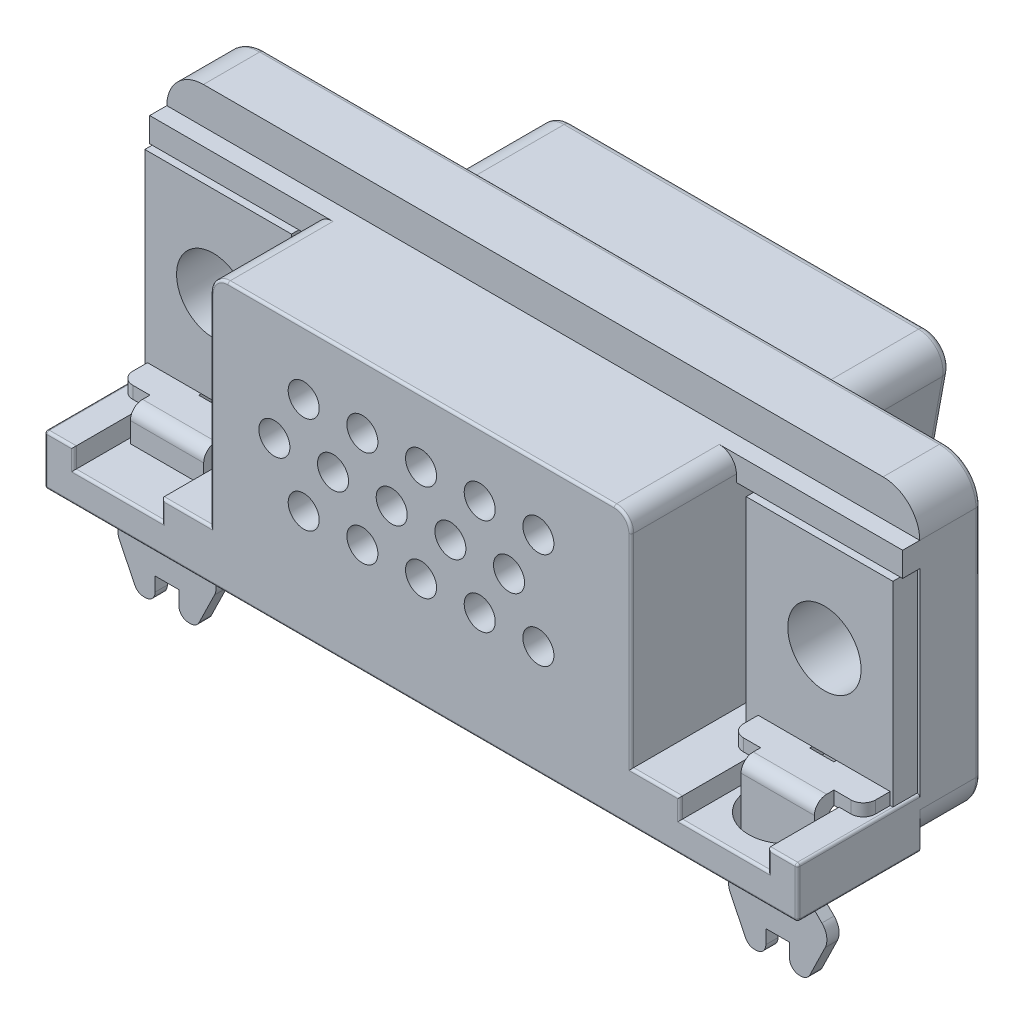
SolidWorks part; units mm, degrees
ref_plane "Спереди" through (0, 0, 0) normal (0, 0, 1) x (1, 0, 0)
ref_plane "Сверху" through (0, 0, 0) normal (0, 1, 0) x (1, 0, 0)
ref_plane "Справа" through (0, 0, 0) normal (1, 0, 0) x (0, 0, -1)
sketch "Эскиз1" plane through (0, 0, 0) normal (0, 0, 1) x (1, 0, 0)
  line L1 (-13.9, -6.275) -> (13.9, -6.275)
  line L2 (-15.4, -4.775) -> (-15.4, 4.775)
  line L3 (-13.9, 6.275) -> (13.9, 6.275)
  line L4 (15.4, -4.775) -> (15.4, 4.775)
  line L5 (-15.4, -6.275) -> (15.4, 6.275) construction
  line L6 (-15.4, 6.275) -> (15.4, -6.275) construction
  arc A0 (13.9, -6.275) -> (15.4, -4.775) centre (13.9, -4.775) ccw
  arc A1 (13.9, 6.275) -> (15.4, 4.775) centre (13.9, 4.775) cw
  arc A2 (-13.9, -6.275) -> (-15.4, -4.775) centre (-13.9, -4.775) cw
  arc A3 (-15.4, 4.775) -> (-13.9, 6.275) centre (-13.9, 4.775) cw
  point P0 (0, 0)
  dimension "D3" = 1.5
  dimension "D1" = 30.8
  dimension "D2" = 12.55
extrude "Бобышка-Вытянуть1" add sketch "Эскиз1" along normal blind 2.5
sketch "Эскиз2" plane through (0, 0, 2.5) normal (0, 0, 1) x (1, 0, 0)
  line L0 (-8.6, -4.225) -> (-8.6, 4.775)
  line L1 (0, 6.275) -> (0, -6.275) construction
  line L2 (13.9, 6.275) -> (-13.9, 6.275) construction
  line L3 (-13.9, -6.275) -> (13.9, -6.275) construction
  line L4 (-8.6, 4.775) -> (8.6, 4.775)
  line L5 (-15.4, 4.775) -> (-15.4, -4.775) construction
  line L6 (8.6, 4.775) -> (8.6, -4.225)
  line L7 (-8.6, -4.225) -> (-10.6, -4.225)
  line L8 (-15.4, -4.225) -> (-15.4, -6.275)
  line L9 (-15.4, -6.275) -> (15.4, -6.275)
  line L10 (8.6, -4.225) -> (10.6, -4.225)
  line L11 (-10.6, -5.0477) -> (-14.2, -5.0477)
  line L12 (15.4, -4.775) -> (15.4, 4.775) construction
  line L13 (-14.2, -5.0477) -> (-14.2, -4.225)
  line L14 (-14.2, -4.225) -> (-15.4, -4.225)
  line L15 (10.6, -5.0477) -> (10.6, -4.225)
  line L16 (10.6, -5.0477) -> (14.2, -5.0477)
  line L17 (14.2, -5.0477) -> (14.2, -4.225)
  line L18 (14.2, -4.225) -> (15.4, -4.225)
  line L19 (15.4, -4.225) -> (15.4, -6.275)
  line L21 (-10.6, -5.0477) -> (-10.6, -4.225)
  dimension "D1" = 9
  dimension "D2" = 17.2
  dimension "D3" = 1.5
  dimension "D4" = 1.2
  dimension "D5" = 0.8227
  dimension "D6" = 3.6
  dimension "D7" = 1.2273
extrude "Бобышка-Вытянуть3" add sketch "Эскиз2" along normal blind 5
sketch "Эскиз3" plane through (0, 0, 2.5) normal (0, 0, 1) x (1, 0, 0)
  line L0 (-6.6576, 4.775) -> (-15.4, 4.775) construction
  line L1 (8.6, 4.775) -> (-8.6, 4.775) construction
  line L2 (-15.4, 4.775) -> (15.4, 4.775)
  line L3 (-15.4, 4.775) -> (-15.4, 3.775)
  line L4 (-15.4, 4.775) -> (-15.4, -4.225) construction
  line L5 (-15.4, 3.775) -> (15.4, 3.775)
  line L6 (15.4, -4.225) -> (15.4, 4.775) construction
  line L7 (15.4, 3.775) -> (15.4, 4.775)
  dimension "D1" = 1
extrude "Бобышка-Вытянуть4" add sketch "Эскиз3" along normal blind 0.7
fillet "Скругление1" radius 0.7 2 edges at (8.6, 4.775, 5.35) (-8.6, 4.775, 5.35)
sketch "Эскиз4" plane through (0, 0, 0) normal (0, 0, -1) x (-1, 0, 0)
  line L0 (0, 6.275) -> (0, -6.275) construction
  line L1 (-13.9, 6.275) -> (13.9, 6.275) construction
  line L2 (13.9, -6.275) -> (-13.9, -6.275) construction
  line L3 (-7.2498, 4.1305) -> (7.2498, 4.1305)
  line L4 (-6.1668, -3.7695) -> (6.1668, -3.7695)
  line L5 (-8.2333, 2.95) -> (-7.1504, -2.95)
  line L6 (8.2333, 2.95) -> (7.1504, -2.95)
  line L7 (-7.6919, 0) -> (7.6919, 0) construction
  arc A0 (6.1668, -3.7695) -> (7.1504, -2.95) centre (6.1668, -2.7695) ccw
  arc A1 (-6.1668, -3.7695) -> (-7.1504, -2.95) centre (-6.1668, -2.7695) cw
  arc A2 (7.2498, 4.1305) -> (8.2333, 2.95) centre (7.2498, 3.1305) cw
  arc A3 (-7.2498, 4.1305) -> (-8.2333, 2.95) centre (-7.2498, 3.1305) ccw
  point P8 (0, 4.1305)
  point P11 (0, -3.7695)
  point P17 (7, -3.7695)
  point P20 (-7, -3.7695)
  point P23 (8.45, 4.1305)
  point P26 (-8.45, 4.1305)
  dimension "D4" = 1
  dimension "D1" = 16.9
  dimension "D2" = 14
  dimension "D3" = 7.9
extrude "Бобышка-Вытянуть5" add sketch "Эскиз4" along normal blind 5.9
sketch "Эскиз5" plane through (0, 0, -5.9) normal (0, 0, -1) x (-1, 0, 0)
  line L8 (6.6586, -2.8597) -> (7.7415, 3.0403)
  line L9 (7.2498, 3.6305) -> (-7.2498, 3.6305)
  line L10 (-7.7415, 3.0403) -> (-6.6586, -2.8597)
  line L11 (-6.1668, -3.2695) -> (6.1668, -3.2695)
  line L12 (6.6586, -2.8597) -> (7.7415, 3.0403)
  line L13 (7.2498, 3.6305) -> (-7.2498, 3.6305)
  line L14 (-7.7415, 3.0403) -> (-6.6586, -2.8597)
  line L15 (-6.1668, -3.2695) -> (6.1668, -3.2695)
  arc A8 (6.1668, -3.2695) -> (6.6586, -2.8597) centre (6.1668, -2.7695) ccw
  arc A9 (7.7415, 3.0403) -> (7.2498, 3.6305) centre (7.2498, 3.1305) ccw
  arc A10 (-7.2498, 3.6305) -> (-7.7415, 3.0403) centre (-7.2498, 3.1305) ccw
  arc A11 (-6.6586, -2.8597) -> (-6.1668, -3.2695) centre (-6.1668, -2.7695) ccw
  arc A12 (6.1668, -3.2695) -> (6.6586, -2.8597) centre (6.1668, -2.7695) ccw
  arc A13 (7.7415, 3.0403) -> (7.2498, 3.6305) centre (7.2498, 3.1305) ccw
  arc A14 (-7.2498, 3.6305) -> (-7.7415, 3.0403) centre (-7.2498, 3.1305) ccw
  arc A15 (-6.6586, -2.8597) -> (-6.1668, -3.2695) centre (-6.1668, -2.7695) ccw
  dimension "D1" = 0.5
extrude "Вырез-Вытянуть1" cut sketch "Эскиз5" against normal blind 0.1
fillet "Скругление2" radius 0.3 16 edges at (-8.018, 3.7706, -5.9) (-7.6919, 0, -5.9) (-6.8069, -3.5378, -5.9) (0, -3.7695, -5.9) (6.8069, -3.5378, -5.9) (7.6919, 0, -5.9) (8.018, 3.7706, -5.9) (0, 4.1305, -5.9) (-8.018, 3.7706, 0) (-7.6919, 0, 0) (-6.8069, -3.5378, 0) (0, -3.7695, 0) (6.8069, -3.5378, 0) (7.6919, 0, 0) (8.018, 3.7706, 0) (0, 4.1305, 0)
sketch "Эскиз6" plane through (0, 0, 0) normal (0, 0, -1) x (-1, 0, 0)
  line L0 (-15.4, 0) -> (15.4, 0) construction
  line L1 (-15.4, -4.775) -> (-15.4, 4.775) construction
  line L2 (15.4, 4.775) -> (15.4, -4.775) construction
  circle A0 centre (-12.5, 0) radius 1.5
  circle A1 centre (12.5, 0) radius 1.5
  dimension "D3" = 3
  dimension "D1" = 12.5
  dimension "D2" = 12.5
extrude "Вырез-Вытянуть2" cut sketch "Эскиз6" against normal through all
sketch "Эскиз7" plane through (0, 0, -5.8) normal (0, 0, -1) x (-1, 0, 0)
  line L0 (7.2498, 3.6305) -> (-7.2498, 3.6305) construction
  line L2 (0, 3.6305) -> (0, -3.2695) construction
  line L3 (-6.1668, -3.2695) -> (6.1668, -3.2695) construction
  line L5 (-4.8, 2.1705) -> (-2.4, 2.1705) construction
  line L6 (-3.6, 2.1705) -> (-3.6, -3.2695) construction
  line L7 (-15.4, -4.775) -> (-15.4, 4.775) construction
  circle A0 centre (-4.8, 2.1705) radius 0.635
  circle A1 centre (-2.4, 2.1705) radius 0.635
  circle A2 centre (0, 2.1705) radius 0.635
  circle A3 centre (2.4, 2.1705) radius 0.635
  circle A4 centre (4.8, 2.1705) radius 0.635
  circle A5 centre (-3.6, 0.1905) radius 0.635
  circle A6 centre (-4.8, -1.7895) radius 0.635
  circle A7 centre (-1.2, 0.1905) radius 0.635
  circle A8 centre (1.2, 0.1905) radius 0.635
  circle A9 centre (3.6, 0.1905) radius 0.635
  circle A10 centre (6, 0.1905) radius 0.635
  circle A11 centre (-2.4, -1.7895) radius 0.635
  circle A12 centre (0, -1.7895) radius 0.635
  circle A13 centre (2.4, -1.7895) radius 0.635
  circle A14 centre (4.8, -1.7895) radius 0.635
  dimension "D1" = 1.27
  dimension "D7" = 1.27
  dimension "D2" = 1.46
  dimension "D3" = 10.6
  dimension "D5" = 2.4
  dimension "D6" = 1.98
  dimension "D8" = 1.98
  dimension "D9" = 5
  dimension "D10" = 1.46
  dimension "D11" = 2.4
  dimension "D12" = 1.98
  dimension "D14" = 2.4
  dimension "D15" = 1.98
  dimension "D16" = 10.6
  dimension "D4" = 5
  dimension "D13" = 5
extrude "Вырез-Вытянуть3" cut sketch "Эскиз7" against normal blind 16.1
fillet "Скругление3" radius 0.15 15 edges at (-5.435, -1.7895, -5.8) (-3.035, -1.7895, -5.8) (-0.635, -1.7895, -5.8) (1.765, -1.7895, -5.8) (4.165, -1.7895, -5.8) (2.965, 0.1905, -5.8) (0.565, 0.1905, -5.8) (-1.835, 0.1905, -5.8) (-4.235, 0.1905, -5.8) (-6.635, 0.1905, -5.8) (-5.435, 2.1705, -5.8) (-3.035, 2.1705, -5.8) (-0.635, 2.1705, -5.8) (1.765, 2.1705, -5.8) (4.165, 2.1705, -5.8)
fillet "Скругление4" radius 0.3 2 edges at (11, 0, 0) (-14, 0, 0)
sketch "Эскиз8" plane through (0, -6.275, 0) normal (0, -1, 0) x (1, 0, 0)
  line L0 (0, 7.5) -> (0, 0) construction
  line L1 (-15.4, 7.5) -> (15.4, 7.5) construction
  line L2 (-13.9, 0) -> (13.9, 0) construction
  circle A0 centre (-12.5, 11.4) radius 1.6
  circle A1 centre (12.5, 5) radius 1.6
  dimension "D1" = 3.2
  dimension "D2" = 12.5
  dimension "D3" = 12.5
  dimension "D4" = 11.4
  dimension "D5" = 5
extrude "Вырез-Вытянуть4" cut sketch "Эскиз8" against normal blind 9.1
fillet "Скругление5" radius 0.2 8 edges at (14.9607, 5.8357, 0) (15.4, 0, 0) (14.9607, -5.8357, 0) (0, -6.275, 0) (-14.9607, -5.8357, 0) (-15.4, 0, 0) (-14.9607, 5.8357, 0) (0, 6.275, 0)
sketch "Эскиз9" plane through (0, 0, 2.5) normal (0, 0, 1) x (1, 0, 0)
  line L0 (-15.3, 3.775) -> (-15.3, -4.225)
  line L1 (-15.4, 3.775) -> (-8.6, 3.775) construction
  line L2 (-14.2, -4.225) -> (-15.4, -4.225) construction
  line L3 (-15.3, -4.225) -> (-9.3, -4.225)
  line L4 (-8.6, -4.225) -> (-10.6, -4.225) construction
  line L5 (-9.3, -4.225) -> (-9.3, 3.775)
  line L6 (-9.3, 3.775) -> (-15.3, 3.775)
  line L7 (-15.4, 3.775) -> (-15.4, -4.225) construction
  line L8 (0, 4.775) -> (0, -6.275) construction
  line L9 (7.9, 4.775) -> (-7.9, 4.775) construction
  line L10 (-15.4, -6.275) -> (15.4, -6.275) construction
  line L11 (9.3, 3.775) -> (15.3, 3.775)
  line L12 (9.3, -4.225) -> (9.3, 3.775)
  line L13 (15.3, -4.225) -> (9.3, -4.225)
  line L14 (15.3, 3.775) -> (15.3, -4.225)
  dimension "D1" = 0.1
  dimension "D2" = 6
extrude "Бобышка-Вытянуть6" add sketch "Эскиз9" along normal blind 1
sketch "Эскиз10" plane through (0, -4.225, 0) normal (0, 1, 0) x (1, 0, 0)
  line L1 (-13.9901, -5.4) -> (-10.9901, -5.4)
  line L2 (-13.9901, -5.4) -> (-13.9901, -4.6)
  line L3 (-13.9901, -4.6) -> (-14.6901, -4.6)
  line L4 (-15.1901, -4.1) -> (-15.1901, -3.5)
  line L5 (-12.4901, -5.4) -> (-12.4901, -4.8291) construction
  line L7 (-15.3, -3.5) -> (-14.2, -3.5) construction
  line L9 (-15.4, -7.5) -> (-15.4, -2.5) construction
  line L10 (-10.9901, -5.4) -> (-10.9901, -4.6)
  line L11 (-10.9901, -4.6) -> (-10.2901, -4.6)
  line L12 (-9.7901, -4.1) -> (-9.7901, -3.5)
  line L13 (-15.1901, -3.5) -> (-9.7901, -3.5)
  line L14 (0, 0) -> (0, -7.5) construction
  line L15 (7.9, -7.5) -> (-7.9, -7.5) construction
  line L16 (12.4901, -5.4) -> (12.4901, -4.8291) construction
  line L17 (14.1, -11.4) -> (10.9, -11.4) construction
  line L18 (15.1901, -3.5) -> (9.7901, -3.5)
  line L19 (9.7901, -4.1) -> (9.7901, -3.5)
  line L20 (10.9901, -4.6) -> (10.2901, -4.6)
  line L21 (10.9901, -5.4) -> (10.9901, -4.6)
  line L22 (15.1901, -4.1) -> (15.1901, -3.5)
  line L23 (13.9901, -4.6) -> (14.6901, -4.6)
  line L24 (13.9901, -5.4) -> (13.9901, -4.6)
  line L25 (13.9901, -5.4) -> (10.9901, -5.4)
  arc A1 (-10.2901, -4.6) -> (-9.7901, -4.1) centre (-10.2901, -4.1) ccw
  arc A2 (-14.6901, -4.6) -> (-15.1901, -4.1) centre (-14.6901, -4.1) cw
  arc A3 (14.6901, -4.6) -> (15.1901, -4.1) centre (14.6901, -4.1) ccw
  arc A4 (10.2901, -4.6) -> (9.7901, -4.1) centre (10.2901, -4.1) cw
  point P22 (-9.7901, -4.6)
  point P25 (-15.1901, -4.6)
  point P47 (15.1901, -4.6)
  point P48 (9.7901, -4.6)
  dimension "D5" = 0.5
  dimension "D1" = 3
  dimension "D2" = 0.8
  dimension "D3" = 1.2
  dimension "D4" = 1.4099
  dimension "D6" = 0.6
extrude "Бобышка-Вытянуть7" add sketch "Эскиз10" along normal blind 0.5
sketch "Эскиз11" plane through (0, -4.225, 0) normal (0, -1, 0) x (1, 0, 0)
  line L0 (-13.9901, 5.4) -> (-10.9901, 5.4)
  line L1 (-10.9901, 5.4) -> (-10.9901, 4.9)
  line L2 (-10.9901, 5.4) -> (-10.9901, 4.6) construction
  line L3 (-10.9901, 4.9) -> (-13.9901, 4.9)
  line L4 (-13.9901, 4.6) -> (-13.9901, 5.4) construction
  line L5 (-13.9901, 4.9) -> (-13.9901, 5.4)
  line L6 (0, 7.5) -> (0, 0) construction
  line L7 (-15.4, 7.5) -> (15.4, 7.5) construction
  line L8 (13.9901, 4.9) -> (13.9901, 5.4)
  line L9 (10.9901, 4.9) -> (13.9901, 4.9)
  line L10 (10.9901, 5.4) -> (10.9901, 4.9)
  line L11 (13.9901, 5.4) -> (10.9901, 5.4)
  dimension "D1" = 0.5
extrude "Бобышка-Вытянуть8" add sketch "Эскиз11" along normal blind 5
fillet "Скругление6" radius 0.5 4 edges at (12.4901, -4.225, 4.9) (12.4901, -3.725, 5.4) (-12.4901, -4.225, 4.9) (-12.4901, -3.725, 5.4)
sketch "Эскиз12" plane through (0, -3.725, 0) normal (0, 1, 0) x (1, 0, 0)
  line L0 (-12.4901, -4.9) -> (-12.4901, -5.981) construction
  line L1 (-13.9901, -4.9) -> (-10.9901, -4.9) construction
  line L2 (-10.6, -7.5) -> (-14.2, -7.5) construction
  line L3 (0, -2.5) -> (0, -7.5) construction
  line L4 (15.4, -2.5) -> (-15.4, -2.5) construction
  line L5 (7.9, -7.5) -> (-7.9, -7.5) construction
  circle A0 centre (-12.4901, -0.8) radius 0.7
  circle A1 centre (12.4901, -0.8) radius 0.7
  dimension "D2" = 1.4
  dimension "D1" = 6.7
extrude "Вырез-Вытянуть5" cut sketch "Эскиз12" against normal up to surface (0.5 mm away) up to face at (-14.9915, -4.225, 4.7671)
sketch "Эскиз13" plane through (0, -3.725, 0) normal (0, 1, 0) x (1, 0, 0)
  line L0 (-12.4901, -0.1) -> (-12.5192, -12.9999) construction
  line L1 (-12.9901, -1.2899) -> (-12.9901, -3.6036)
  line L2 (-13.9901, -4.6) -> (-13.9901, -4.9) construction
  line L3 (-11.9954, -1.2921) -> (-12.0059, -3.6058)
  line L4 (-12.9901, -3.6036) -> (-12.0059, -3.6058)
  line L5 (0, 0) -> (0, -7.5) construction
  line L6 (7.9, -7.5) -> (-7.9, -7.5) construction
  circle A0 centre (-12.4901, -0.8) radius 0.7 construction
  arc A2 (-12.9901, -1.2899) -> (-11.9955, -1.2953) centre (-12.4901, -0.8) ccw
  dimension "D4" = 2.3137
  dimension "D1" = 1
  dimension "D2" = 2.3137
  dimension "D3" = 0.9842
extrude "Вырез-Вытянуть6" cut sketch "Эскиз13" against normal blind 7
mirror "Зеркальное отражение1" about plane through (0, 0, 0) normal (1, 0, 0) of "Вырез-Вытянуть6"
sketch "Эскиз14" plane through (0, 0, 2.5) normal (0, 0, -1) x (-1, 0, 0)
  circle A0 centre (12.5, 0) radius 1.5 construction
  circle A1 centre (12.5, 0) radius 1.5
  circle A2 centre (-12.5, 0) radius 1.5 construction
  circle A3 centre (-12.5, 0) radius 1.5
extrude "Вырез-Вытянуть7" cut sketch "Эскиз14" against normal blind 7
sketch "Эскиз15" plane through (0, 0, 5.4) normal (0, 0, 1) x (1, 0, 0)
  line L0 (10.9901, -7.575) -> (10.6832, -7.8818)
  line L1 (10.9901, -4.225) -> (10.9901, -9.225) construction
  line L2 (10.549, -8.6837) -> (11.1758, -9.9686)
  line L3 (11.5353, -10.1932) -> (11.6043, -10.1932)
  line L4 (12.0043, -9.795) -> (12.014, -7.575)
  line L5 (12.014, -9.225) -> (12.014, -4.225) construction
  line L6 (12.014, -7.575) -> (10.9901, -7.575)
  line L7 (-15.4, -6.275) -> (15.4, -6.275) construction
  line L8 (12.4901, -3.725) -> (12.4901, -16.3735) construction
  line L10 (12.9661, -7.575) -> (13.9901, -7.575)
  line L11 (12.9758, -9.795) -> (12.9661, -7.575)
  line L12 (13.4448, -10.1932) -> (13.3758, -10.1932)
  line L13 (14.4311, -8.6837) -> (13.8043, -9.9686)
  line L14 (13.9901, -7.575) -> (14.2969, -7.8818)
  line L15 (0, 0) -> (0, -13.07) construction
  line L16 (-13.9901, -7.575) -> (-14.2969, -7.8818)
  line L17 (-14.4311, -8.6837) -> (-13.8043, -9.9686)
  line L18 (-13.4448, -10.1932) -> (-13.3758, -10.1932)
  line L19 (-12.9758, -9.795) -> (-12.9661, -7.575)
  line L20 (-12.9661, -7.575) -> (-13.9901, -7.575)
  line L21 (-12.014, -7.575) -> (-10.9901, -7.575)
  line L22 (-12.0043, -9.795) -> (-12.014, -7.575)
  line L23 (-11.5353, -10.1932) -> (-11.6043, -10.1932)
  line L24 (-10.549, -8.6837) -> (-11.1758, -9.9686)
  line L25 (-10.9901, -7.575) -> (-10.6832, -7.8818)
  line L26 (13.9901, -4.225) -> (13.9901, -9.225) construction
  arc A0 (10.6832, -7.8818) -> (10.549, -8.6837) centre (11.1782, -8.3768) ccw
  arc A1 (11.6043, -10.1932) -> (12.0043, -9.795) centre (11.6043, -9.7932) ccw
  arc A2 (11.1758, -9.9686) -> (11.5353, -10.1932) centre (11.5353, -9.7932) ccw
  arc A3 (13.8043, -9.9686) -> (13.4448, -10.1932) centre (13.4448, -9.7932) cw
  arc A4 (13.3758, -10.1932) -> (12.9758, -9.795) centre (13.3758, -9.7932) cw
  arc A5 (14.2969, -7.8818) -> (14.4311, -8.6837) centre (13.8019, -8.3768) cw
  arc A6 (-14.2969, -7.8818) -> (-14.4311, -8.6837) centre (-13.8019, -8.3768) ccw
  arc A7 (-13.3758, -10.1932) -> (-12.9758, -9.795) centre (-13.3758, -9.7932) ccw
  arc A8 (-13.8043, -9.9686) -> (-13.4448, -10.1932) centre (-13.4448, -9.7932) ccw
  arc A9 (-11.1758, -9.9686) -> (-11.5353, -10.1932) centre (-11.5353, -9.7932) cw
  arc A10 (-11.6043, -10.1932) -> (-12.0043, -9.795) centre (-11.6043, -9.7932) cw
  arc A11 (-10.6832, -7.8818) -> (-10.549, -8.6837) centre (-11.1782, -8.3768) cw
  point P13 (10.3301, -8.2349)
  point P16 (12.0025, -10.1932)
  point P19 (11.2854, -10.1932)
  point P35 (13.6947, -10.1932)
  point P36 (12.9776, -10.1932)
  point P37 (14.65, -8.2349)
  point P63 (-14.65, -8.2349)
  point P64 (-12.9776, -10.1932)
  point P65 (-13.6947, -10.1932)
  point P66 (-11.2854, -10.1932)
  point P67 (-12.0025, -10.1932)
  point P68 (-10.3301, -8.2349)
  dimension "D7" = 0.7
  dimension "D8" = 0.4
  dimension "D1" = 1.3
  dimension "D2" = 0.9333
  dimension "D3" = 45
  dimension "D4" = 2.1789
  dimension "D5" = 0.7171
  dimension "D6" = 2.6183
extrude "Бобышка-Вытянуть9" add sketch "Эскиз15" against normal blind 0.5
fillet "Скругление9" radius 0.1 22 edges at (9.6, -4.225, 7.5) (10.6, -4.6364, 7.5) (12.4, -5.0477, 7.5) (14.2, -4.6364, 7.5) (14.8, -4.225, 7.5) (15.4, -5.25, 7.5) (0, -6.275, 7.5) (-15.4, -5.25, 7.5) (-14.8, -4.225, 7.5) (-14.2, -4.6364, 7.5) (-12.4, -5.0477, 7.5) (-10.6, -4.6364, 7.5) (-9.6, -4.225, 7.5) (-8.6, -0.075, 7.5) (-8.395, 4.57, 7.5) (0, 4.775, 7.5) (8.395, 4.57, 7.5) (8.6, -0.075, 7.5) (15.4, -6.275, 5) (-15.4, -6.275, 5)
